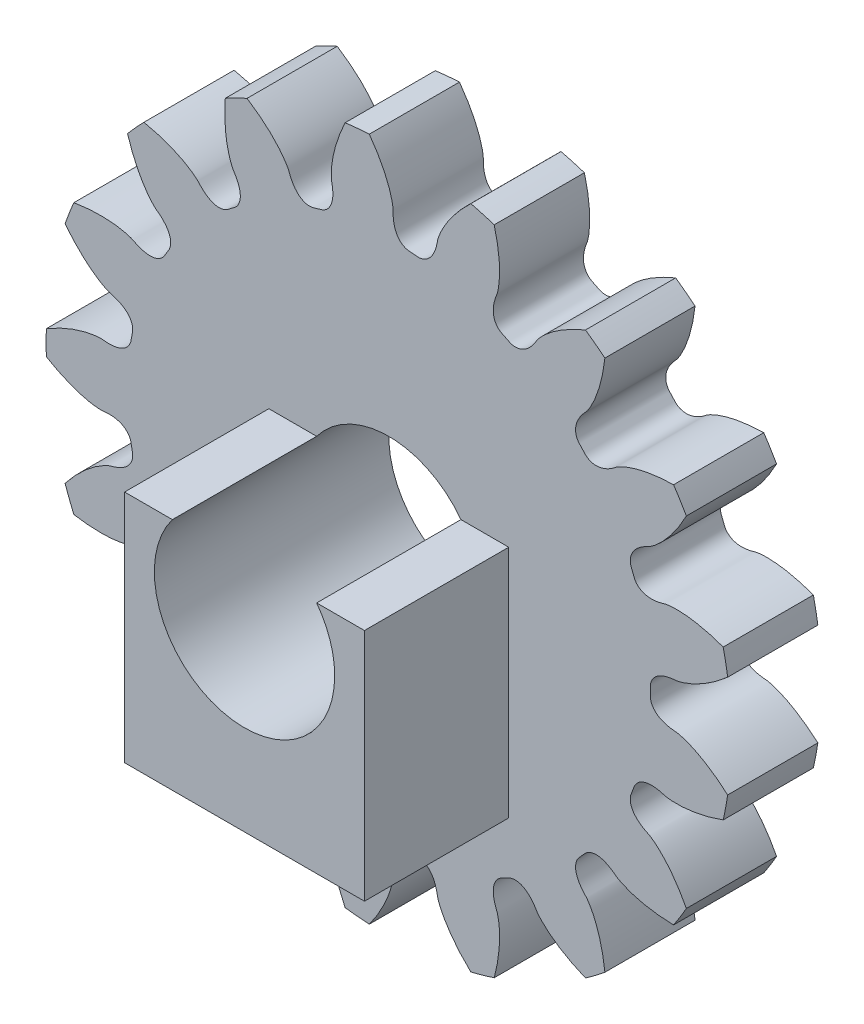
SolidWorks part; units mm, degrees
material "POM 乙缩醛共聚物"
ref_plane "前视基准面" through (0, 0, 0) normal (0, 0, 1) x (1, 0, 0)
ref_plane "上视基准面" through (0, 0, 0) normal (0, 1, 0) x (1, 0, 0)
ref_plane "右视基准面" through (0, 0, 0) normal (1, 0, 0) x (0, 0, -1)
ref_axis "基准轴1" through (0, 0, 55) along (0, 0, -1)
sketch "旋转草图小直齿轮" plane through (0, 0, 0) normal (1, 0, 0) x (0, 0, -1)
  line L0 (0, 0) -> (1, 0) construction
  line L1 (-2.5, 0) -> (-2.5, 19)
  line L2 (-2.5, 19) -> (2.5, 19)
  line L3 (2.5, 19) -> (2.5, 0)
  line L4 (2.5, 0) -> (-2.5, 0)
  dimension "D1" = 5
  dimension "D2" = 19
revolve "小直齿轮" add sketch "旋转草图小直齿轮" angle 360 about L0
sketch "齿草图小直齿轮" plane through (0, 0, 0) normal (0, 0, 1) x (1, 0, 0)
  arc A0 (18.8777, 2.9059) -> (18.8777, -2.9059) centre (0, 0) cw
  spline S0 degree 3 poles (18.8777, -2.9059) (18.8357, -2.8681) (18.7727, -2.8123) (18.6883, -2.7394) (18.6258, -2.6863) (18.5637, -2.6344) (18.502, -2.5837) (18.4407, -2.5341) (18.3798, -2.4858) (18.3194, -2.4386) (18.2595, -2.3925) (18.2, -2.3476) (18.141, -2.3038) (18.0826, -2.2612) (18.0246, -2.2196) (17.9672, -2.1791) (17.9104, -2.1397) (17.8541, -2.1014) (17.7984, -2.0642) (17.7433, -2.028) (17.6888, -1.9928) (17.6349, -1.9586) (17.5817, -1.9255) (17.5291, -1.8933) (17.4771, -1.8622) (17.4259, -1.832) (17.3753, -1.8027) (17.3254, -1.7744) (17.2762, -1.7471) (17.2277, -1.7206) (17.18, -1.6951) (17.133, -1.6704) (17.0867, -1.6467) (17.0412, -1.6237) (16.9965, -1.6017) (16.9526, -1.5804) (16.9095, -1.56) (16.8672, -1.5404) (16.8257, -1.5216) (16.785, -1.5036) (16.7452, -1.4863) (16.7062, -1.4697) (16.668, -1.4539) (16.6308, -1.4388) (16.5944, -1.4244) (16.5589, -1.4107) (16.5243, -1.3977) (16.4905, -1.3853) (16.4577, -1.3736) (16.4258, -1.3625) (16.3949, -1.3519) (16.3649, -1.342) (16.3358, -1.3327) (16.3076, -1.3239) (16.2804, -1.3156) (16.2542, -1.3079) (16.2289, -1.3007) (16.2047, -1.2939) (16.1814, -1.2877) (16.1591, -1.2819) (16.1377, -1.2766) (16.1174, -1.2717) (16.0981, -1.2671) (16.0798, -1.263) (16.0625, -1.2593) (16.0462, -1.2559) (16.031, -1.2529) (16.0168, -1.2502) (16.0036, -1.2478) (15.9914, -1.2457) (15.9803, -1.2438) (15.9703, -1.2423) (15.9612, -1.2409) (15.9533, -1.2398) (15.9464, -1.2389) (15.9405, -1.2382) (15.8782, -1.231) (15.7988, -1.228) (15.7037, -1.216) (15.6495, -1.2083) (15.5963, -1.1996) (15.544, -1.19) (15.4927, -1.1794) (15.4423, -1.1677) (15.3928, -1.1551) (15.3442, -1.1414) (15.2965, -1.1266) (15.2496, -1.1108) (15.2035, -1.0937) (15.1582, -1.0755) (15.1136, -1.056) (15.0698, -1.0351) (15.0267, -1.0127) (14.9843, -0.9888) (14.9426, -0.9632) (14.9016, -0.9357) (14.8613, -0.9062) (14.8218, -0.8744) (14.7832, -0.8402) (14.7455, -0.8034) (14.709, -0.7636) (14.674, -0.7206) (14.6407, -0.6743) (14.6095, -0.6245) (14.581, -0.5711) (14.5558, -0.5142) (14.5343, -0.4538) (14.5174, -0.3904) (14.5054, -0.3246) (14.4997, -0.2626) (14.4972, -0.1542) (14.5022, 0) (14.4972, 0.1542) (14.4997, 0.2626) (14.5054, 0.3246) (14.5174, 0.3904) (14.5343, 0.4538) (14.5558, 0.5142) (14.581, 0.5711) (14.6095, 0.6245) (14.6407, 0.6743) (14.674, 0.7206) (14.709, 0.7636) (14.7455, 0.8034) (14.7832, 0.8402) (14.8218, 0.8744) (14.8613, 0.9062) (14.9016, 0.9357) (14.9426, 0.9632) (14.9843, 0.9888) (15.0267, 1.0127) (15.0698, 1.0351) (15.1136, 1.056) (15.1582, 1.0755) (15.2035, 1.0937) (15.2496, 1.1108) (15.2965, 1.1266) (15.3442, 1.1414) (15.3928, 1.1551) (15.4423, 1.1677) (15.4927, 1.1794) (15.544, 1.19) (15.5963, 1.1996) (15.6495, 1.2083) (15.7037, 1.216) (15.7988, 1.228) (15.8782, 1.231) (15.9405, 1.2382) (15.9464, 1.2389) (15.9533, 1.2398) (15.9612, 1.2409) (15.9703, 1.2423) (15.9803, 1.2438) (15.9914, 1.2457) (16.0036, 1.2478) (16.0168, 1.2502) (16.031, 1.2529) (16.0462, 1.2559) (16.0625, 1.2593) (16.0798, 1.263) (16.0981, 1.2671) (16.1174, 1.2717) (16.1377, 1.2766) (16.1591, 1.2819) (16.1814, 1.2877) (16.2047, 1.2939) (16.2289, 1.3007) (16.2542, 1.3079) (16.2804, 1.3156) (16.3076, 1.3239) (16.3358, 1.3327) (16.3649, 1.342) (16.3949, 1.3519) (16.4258, 1.3625) (16.4577, 1.3736) (16.4905, 1.3853) (16.5243, 1.3977) (16.5589, 1.4107) (16.5944, 1.4244) (16.6308, 1.4388) (16.668, 1.4539) (16.7062, 1.4697) (16.7452, 1.4863) (16.785, 1.5036) (16.8257, 1.5216) (16.8672, 1.5404) (16.9095, 1.56) (16.9526, 1.5804) (16.9965, 1.6017) (17.0412, 1.6237) (17.0867, 1.6467) (17.133, 1.6704) (17.18, 1.6951) (17.2277, 1.7206) (17.2762, 1.7471) (17.3254, 1.7744) (17.3753, 1.8027) (17.4259, 1.832) (17.4771, 1.8622) (17.5291, 1.8933) (17.5817, 1.9255) (17.6349, 1.9586) (17.6888, 1.9928) (17.7433, 2.028) (17.7984, 2.0642) (17.8541, 2.1014) (17.9104, 2.1397) (17.9672, 2.1791) (18.0246, 2.2196) (18.0826, 2.2612) (18.141, 2.3038) (18.2, 2.3476) (18.2595, 2.3925) (18.3194, 2.4386) (18.3798, 2.4858) (18.4407, 2.5341) (18.502, 2.5837) (18.5637, 2.6344) (18.6258, 2.6863) (18.6883, 2.7394) (18.7727, 2.8123) (18.8357, 2.8681) (18.8777, 2.9059) knots 0 0 0 0 0.015162 0.022599 0.02994 0.037185 0.044335 0.051388 0.058345 0.065206 0.071972 0.078641 0.085214 0.091692 0.098073 0.104359 0.110548 0.116642 0.12264 0.128541 0.134347 0.140057 0.145671 0.151188 0.15661 0.161936 0.167166 0.1723 0.177338 0.18228 0.187126 0.191876 0.196531 0.201089 0.205551 0.209917 0.214188 0.218362 0.22244 0.226423 0.230309 0.2341 0.237794 0.241393 0.244896 0.248302 0.251613 0.254828 0.257946 0.260969 0.263896 0.266727 0.269462 0.272101 0.274644 0.277091 0.279442 0.281697 0.283856 0.285919 0.287887 0.289758 0.291533 0.293213 0.294796 0.296283 0.297675 0.29897 0.30017 0.301273 0.302281 0.303193 0.304008 0.304728 0.305352 0.30588 0.306311 0.322195 0.327168 0.332064 0.336888 0.341642 0.346331 0.350958 0.355527 0.360044 0.364514 0.368944 0.373339 0.377707 0.382057 0.386397 0.390737 0.39509 0.399465 0.403878 0.408341 0.41287 0.417481 0.42219 0.427014 0.431967 0.437065 0.442317 0.44773 0.453305 0.459036 0.464909 0.470899 0.476976 0.481621 0.5 0.518379 0.523024 0.529101 0.535091 0.540964 0.546695 0.55227 0.557683 0.562935 0.568033 0.572986 0.57781 0.582519 0.58713 0.591659 0.596122 0.600535 0.60491 0.609263 0.613603 0.617943 0.622293 0.626661 0.631056 0.635486 0.639956 0.644473 0.649042 0.653669 0.658358 0.663112 0.667936 0.672832 0.677805 0.693689 0.69412 0.694648 0.695272 0.695992 0.696807 0.697719 0.698727 0.69983 0.70103 0.702325 0.703717 0.705204 0.706787 0.708467 0.710242 0.712113 0.714081 0.716144 0.718303 0.720558 0.722909 0.725356 0.727899 0.730538 0.733273 0.736104 0.739031 0.742054 0.745172 0.748387 0.751698 0.755104 0.758607 0.762206 0.7659 0.769691 0.773577 0.77756 0.781638 0.785812 0.790083 0.794449 0.798911 0.803469 0.808124 0.812874 0.81772 0.822662 0.8277 0.832834 0.838064 0.84339 0.848812 0.854329 0.859943 0.865653 0.871459 0.87736 0.883358 0.889452 0.895641 0.901927 0.908308 0.914786 0.921359 0.928028 0.934794 0.941655 0.948612 0.955665 0.962815 0.97006 0.977401 0.984838 1 1 1 1
extrude "齿拉伸切除小直齿轮" cut sketch "齿草图小直齿轮" against normal blind 10 and the other way blind 10
pattern_circular "齿形小直齿轮" count 17 every 21.176 about axis through (0, 0, 55) along (0, 0, -1) of "齿拉伸切除小直齿轮"
sketch "孔旋转草图" plane through (0, 0, 0) normal (1, 0, 0) x (0, 0, -1)
  line L0 (0, 0) -> (1, 0) construction
  line L1 (-10, 0) -> (10, 0)
  line L2 (10, 0) -> (10, 5)
  line L3 (10, 5) -> (-10, 5)
  line L4 (-10, 5) -> (-10, 0)
  dimension "TaperSide1" = 5
  dimension "TaperSide2" = 5
revolve "孔旋转切除" cut sketch "孔旋转草图" angle 360 about L0
sketch "辅助草图小直齿轮" plane through (0, 0, 0) normal (0, 0, 1) x (1, 0, 0)
  circle A0 centre (0, 0) radius 17 construction
  circle A1 centre (0, 0) radius 15.9748 construction
  circle A2 centre (0, 0) radius 15.9784 construction
  circle A3 centre (0, 0) radius 19 construction
  circle A4 centre (0, 0) radius 14.5 construction
  dimension "PitchDiameter" = 34
  dimension "BaseDiameter" = 31.9495
  dimension "FormDiameter" = 31.9568
  dimension "MajorDiameter" = 38
  dimension "MinorDiameter" = 29
sketch "草图1" plane through (0, 0, 2.5) normal (0, 0, 1) x (1, 0, 0)
  line L0 (-6.65, 3) -> (-4, 3)
  line L1 (-6.65, 3) -> (-6.65, -10)
  line L2 (-6.65, -10) -> (6.65, -10)
  line L3 (6.65, -10) -> (6.65, 3)
  line L4 (0, 0) -> (0, 7.0829) construction
  line L5 (4, 3) -> (6.65, 3)
  circle A0 centre (0, 0) radius 5 construction
  arc A1 (-4, 3) -> (4, 3) centre (0, 0) ccw
  dimension "D1" = 3
  dimension "D2" = 13.3
  dimension "D3" = 10
extrude "凸台-拉伸1" add sketch "草图1" along normal blind 8
sketch "草图2" plane through (0, 0, -2.5) normal (0, 0, -1) x (-1, 0, 0)
  circle A0 centre (0, 0) radius 22.5
  circle A1 centre (0, 0) radius 19 construction
  dimension "D1" = 3.5
